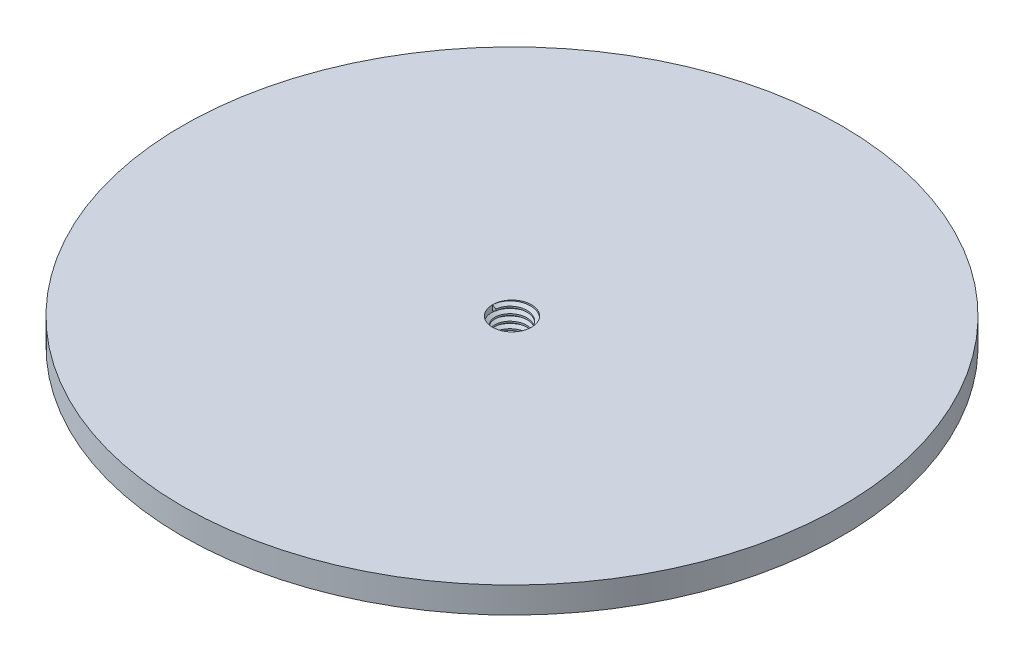
SolidWorks part; units mm, degrees
material "6061 Alloy"
ref_plane "Front Plane" through (0, 0, 0) normal (0, 0, 1) x (1, 0, 0)
ref_plane "Top Plane" through (0, 0, 0) normal (0, 1, 0) x (1, 0, 0)
ref_plane "Right Plane" through (0, 0, 0) normal (1, 0, 0) x (0, 0, -1)
sketch "Sketch1" plane through (0, 0, 0) normal (0, 1, 0) x (1, 0, 0)
  circle A0 centre (0, 0) radius 80.391
  dimension "D1" = 160.782
extrude "Boss-Extrude1" add sketch "Sketch1" along normal blind 6.35
sketch "Sketch3" plane through (0, 6.35, 0) normal (0, 1, 0) x (1, 0, 0)
  circle A0 centre (0, 0) radius 4.7625
  dimension "D1" = 9.525
extrude "Cut-Extrude2" cut sketch "Sketch3" against normal through all
thread "Thread1" pitch 1.5875 method extrude profile "Thread Profile1" start angle 0, offset 0, length 0, pitch 1.5875, diameter 9.525
ref_plane "Plane1" through (-4.7625, 6.35, 0) normal (0, 0, 1) x (-1, 0, 0)
sketch "Thread Profile1" plane through (-4.7625, 6.35, 0) normal (0, 0, 1) x (-1, 0, 0)
  line L0 (0, 0) -> (0, 1.5875) construction
  line L11 (0, 0) -> (0, 1.3891)
  line L12 (0, 1.3891) -> (-0.8593, 0.893)
  line L13 (-0.8593, 0.893) -> (-0.8593, 0.4961)
  line L15 (-0.8593, 0.4961) -> (0, 0)
  line L17 (-0.8593, 0.6945) -> (0, 0.6945) construction
  point P2 (0, 0)
  dimension "Pitch" = 1.5875
  dimension "Profile_Angle" = 60
  dimension "Profile_Land" = 0.3969
  dimension "Profile_Height" = 0.8593
